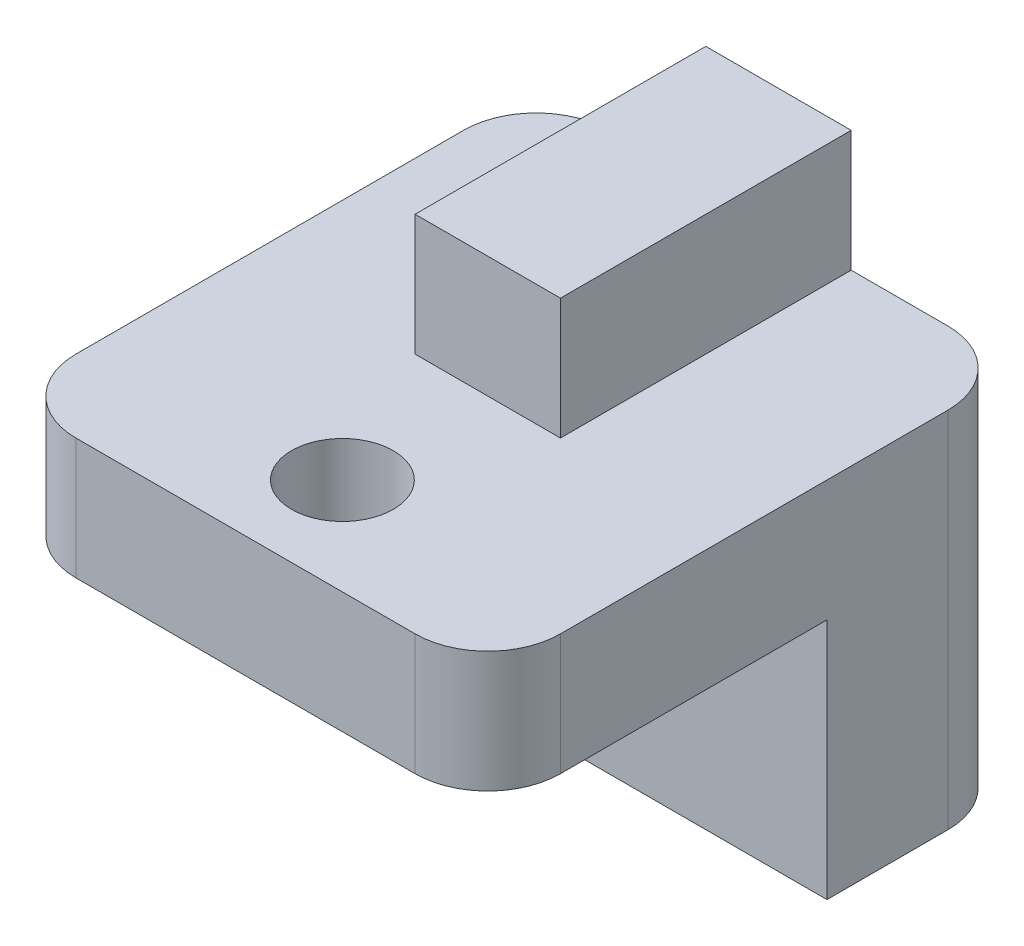
SolidWorks part; units mm, degrees
ref_plane "前视基准面" through (0, 0, 0) normal (0, 0, 1) x (1, 0, 0)
ref_plane "上视基准面" through (0, 0, 0) normal (0, 1, 0) x (1, 0, 0)
ref_plane "右视基准面" through (0, 0, 0) normal (1, 0, 0) x (0, 0, -1)
sketch "草图1" plane through (0, 0, 0) normal (0, 1, 0) x (1, 0, 0)
  line L0 (10, 31.5863) -> (10, -15.5509) construction
  line L1 (0, 0) -> (20, 0)
  line L2 (0, 0) -> (0, 22)
  line L3 (0, 22) -> (20, 22)
  line L4 (20, 0) -> (20, 22)
  line L5 (-9.9752, 10) -> (35.1948, 10) construction
  line L7 (7, 22) -> (13, 22)
  line L8 (7, 22) -> (7, 10)
  line L9 (7, 10) -> (13, 10)
  line L10 (13, 22) -> (13, 10)
  line L11 (7, 22) -> (13, 10) construction
  line L12 (7, 10) -> (13, 22) construction
  circle A0 centre (10, 4) radius 2.1
  circle A1 centre (6.75, 17) radius 1
  circle A2 centre (13.25, 17) radius 1
  point P11 (10, 16)
  dimension "D7" = 4.2
  dimension "D11" = 2
  dimension "D1" = 20
  dimension "D2" = 22
  dimension "D3" = 6
  dimension "D4" = 10
  dimension "D5" = 12
  dimension "D6" = 12
  dimension "D8" = 4
  dimension "D9" = 5
  dimension "D10" = 3.25
extrude "凸台-拉伸1" add sketch "草图1" along normal blind 5 contours L10 A2 L9 L8 A1 L3 L2 L1 L4 A0 | L10 A2 L3 L8 A1 L9 | A2 L10 | A2 L10 | L8 A1 | L8 A1 region at (0.2973, 0, -11) region at (10, 0, -15.9692) region at (7.3124, 0, -17) region at (6.457, 0, -17) region at (13.543, 0, -17) region at (12.6876, 0, -17)
extrude "凸台-拉伸2" add sketch "草图1<3>" along normal blind 5 from vertex contours L10 A2 L3 L8 A1 L9 | A2 L10 | L8 A1 region at (10, 0, -15.9692) region at (7.3124, 0, -17) region at (12.6876, 0, -17) starting at point (20, 5, -22)
sketch "草图1<3>" plane through (0, 0, 0) normal (0, 1, 0) x (1, 0, 0) same geometry as "草图1"
fillet "圆角2" radius 3 4 edges at (20, 2.5, 0) (0, 2.5, 0) (0, 2.5, -22) (20, 2.5, -22)
sketch "草图2" plane through (0, 0, 0) normal (0, -1, 0) x (1, 0, 0)
  line L0 (3, -22) -> (17, -22) construction
  line L1 (20, -3) -> (20, -19) construction
  line L2 (0, -3) -> (0, -19) construction
  line L3 (3, -22) -> (17, -22)
  line L4 (20, -14) -> (20, -19)
  line L5 (0, -14) -> (0, -19)
  line L6 (20, -14) -> (0, -14)
  arc A0 (17, -22) -> (20, -19) centre (17, -19) ccw construction
  arc A1 (0, -19) -> (3, -22) centre (3, -19) ccw construction
  arc A2 (17, -22) -> (20, -19) centre (17, -19) ccw
  arc A3 (0, -19) -> (3, -22) centre (3, -19) ccw
  dimension "D1" = 8
extrude "凸台-拉伸3" add sketch "草图2" along normal blind 10
